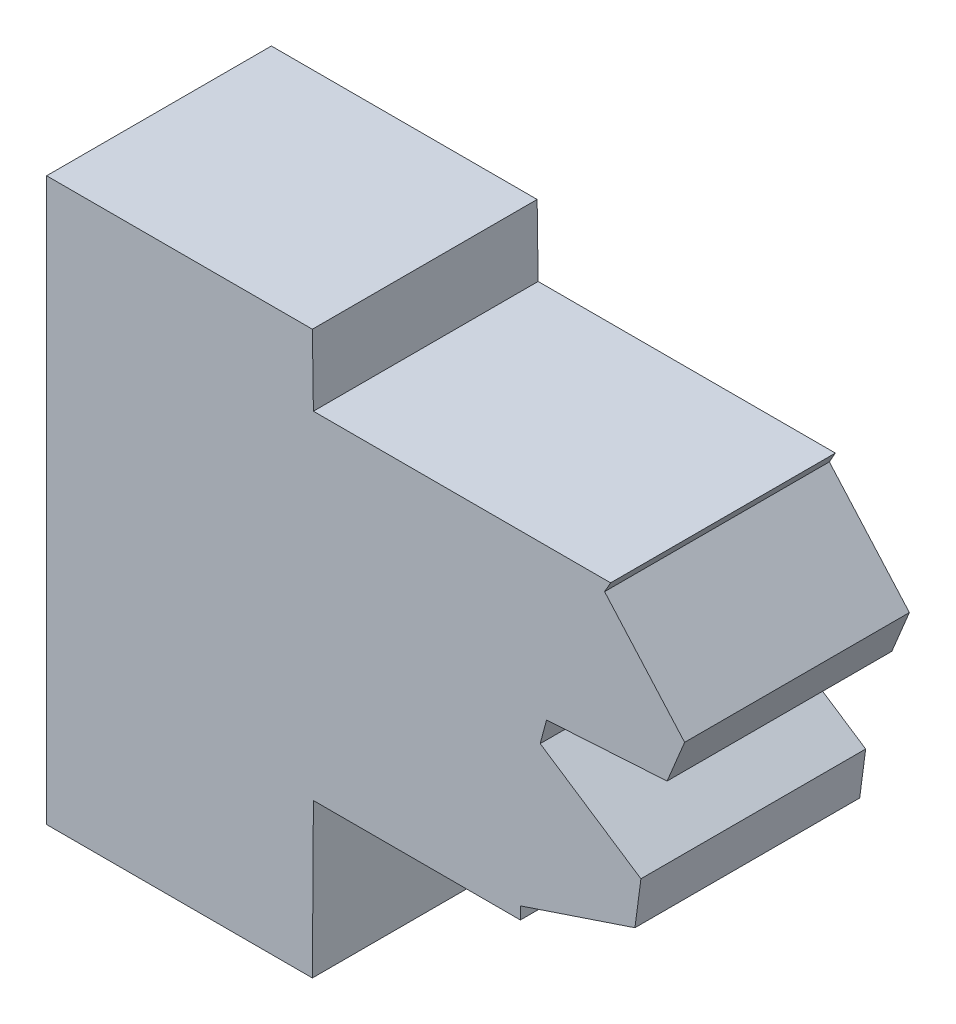
SolidWorks part; units mm, degrees
ref_plane "Front Plane" through (0, 0, 0) normal (0, 0, 1) x (1, 0, 0)
ref_plane "Top Plane" through (0, 0, 0) normal (0, 1, 0) x (1, 0, 0)
ref_plane "Right Plane" through (0, 0, 0) normal (1, 0, 0) x (0, 0, -1)
sketch "Sketch1" plane through (0, 0, 0) normal (0, 0, 1) x (1, 0, 0)
  line L0 (4.7478, 2.7448) -> (8.4321, 2.7448)
  line L1 (4.7478, 2.7448) -> (4.73, 0)
  line L2 (4.7478, 8.7448) -> (10.0378, 8.7448)
  line L3 (8.4321, 2.7448) -> (8.4321, 2.9629)
  line L4 (4.73, 0) -> (0, 0)
  line L5 (8.4321, 2.9629) -> (10.4707, 3.6448)
  line L6 (10.4707, 3.6448) -> (10.5771, 4.4531)
  line L7 (10.5771, 4.4531) -> (8.7845, 5.6394)
  line L8 (8.7845, 5.6394) -> (8.8973, 6.0607)
  line L9 (8.8973, 6.0607) -> (11.043, 6.1918)
  line L10 (11.043, 6.1918) -> (11.355, 6.9451)
  line L11 (11.355, 6.9451) -> (9.9305, 8.5549)
  line L12 (9.9305, 8.5549) -> (10.0378, 8.7448)
  line L13 (4.73, 10) -> (0, 10)
  line L14 (0, 0) -> (0, 10)
  line L15 (4.73, 10) -> (4.7478, 8.7448)
  dimension "D1" = 4.73
  dimension "D2" = 4.7478
  dimension "D3" = 1.2552
  dimension "D4" = 5.29
  dimension "D5" = 0.4362
  dimension "D6" = 2.1496
  dimension "D7" = 0.8153
  dimension "D8" = 0.2181
  dimension "D9" = 8.5549
  dimension "D10" = 6.9451
  dimension "D11" = 6.1918
  dimension "D12" = 6.0607
  dimension "D13" = 2.7448
  dimension "D14" = 5.6394
  dimension "D15" = 4.4531
  dimension "D16" = 3.6448
  dimension "D23" = 10
extrude "Boss-Extrude1" add sketch "Sketch1" along normal blind 4
equation "\"D4@Sketch1\" = \"ThumbLinkLengthMCP@Sketch1@thumbMovingBracketDown.SLDPRT\" - 13.7'Toothed Mechanism"
